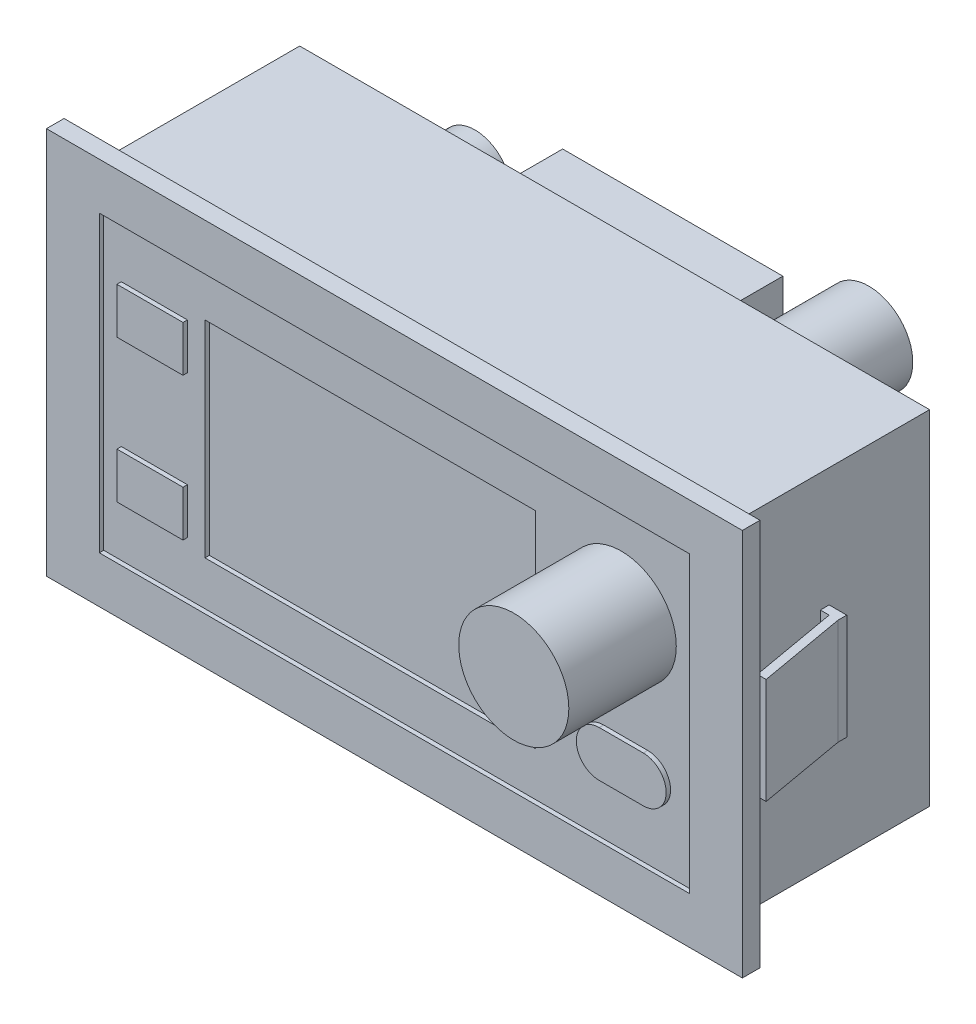
SolidWorks part; units mm, degrees
ref_plane "前视基准面" through (0, 0, 0) normal (0, 0, 1) x (1, 0, 0)
ref_plane "上视基准面" through (0, 0, 0) normal (0, 1, 0) x (1, 0, 0)
ref_plane "右视基准面" through (0, 0, 0) normal (1, 0, 0) x (0, 0, -1)
other "Configuration Table"
sketch "草图1" plane through (0, 0, 0) normal (0, 0, 1) x (1, 0, 0)
  line L0 (62.75, -30.1) -> (67.75, -30.1) construction
  line L1 (0, 0) -> (79, 0)
  line L2 (0, 0) -> (0, -44)
  line L3 (0, -44) -> (79, -44)
  line L4 (79, 0) -> (79, -44)
  line L5 (6, -5.3) -> (73, -5.3)
  line L6 (6, -5.3) -> (6, -38.7)
  line L7 (6, -38.7) -> (73, -38.7)
  line L8 (73, -5.3) -> (73, -38.7)
  line L11 (83.562, -21.4) -> (126.0812, -21.4) construction
  line L12 (17.5, -10.3) -> (55, -10.3)
  line L13 (17.5, -10.3) -> (17.5, -33.7)
  line L14 (17.5, -33.7) -> (55, -33.7)
  line L15 (55, -10.3) -> (55, -33.7)
  line L16 (8, -11.3) -> (15.5, -11.3)
  line L17 (8, -11.3) -> (8, -16.5)
  line L18 (8, -16.5) -> (15.5, -16.5)
  line L19 (15.5, -11.3) -> (15.5, -16.5)
  line L20 (8, -27.5) -> (15.5, -27.5)
  line L21 (8, -27.5) -> (8, -32.7)
  line L22 (8, -32.7) -> (15.5, -32.7)
  line L23 (15.5, -27.5) -> (15.5, -32.7)
  line L24 (59, 18.2066) -> (59, 8.2411) construction
  line L25 (62.75, -27.5) -> (67.75, -27.5)
  line L26 (62.75, -32.7) -> (67.75, -32.7)
  circle A0 centre (65.25, -15.15) radius 6.25
  arc A3 (62.75, -27.5) -> (62.75, -32.7) centre (62.75, -30.1) ccw
  arc A4 (67.75, -32.7) -> (67.75, -27.5) centre (67.75, -30.1) ccw
  point P11 (8, -13.9)
  point P14 (65.25, -30.1)
  point P35 (0, 0)
  point P36 (15.5, -30.1)
  dimension "D7" = 12.5
  dimension "D1" = 79
  dimension "D2" = 44
  dimension "D3" = 5.3
  dimension "D4" = 6
  dimension "D5" = 6
  dimension "D6" = 5.3
  dimension "D8" = 21.4
  dimension "D9" = 20
  dimension "D10" = 11.5
  dimension "D11" = 18
  dimension "D12" = 5
  dimension "D13" = 5
  dimension "D14" = 2
  dimension "D15" = 2
  dimension "D16" = 6
  dimension "D17" = 6
  dimension "D18" = 5.2
  dimension "D19" = 5.2
  dimension "D20" = 5
extrude "凸台-拉伸1" add sketch "草图1" against normal blind 12.2 contours A0
extrude "凸台-拉伸2" add sketch "草图1<3>" against normal blind 2 from surface separate body contours L4 L3 L2 L1 | L8 L7 L6 L5 starting at face at (71.5, -15.15, -12.2)
sketch "草图1<3>" plane through (0, 0, 0) normal (0, 0, 1) x (1, 0, 0) same geometry as "草图1"
extrude "凸台-拉伸3" add sketch "草图1<4>" along normal blind 1.5 from surface contours L8 L7 L6 L5 starting at face at (39.5, -22, -14.2)
sketch "草图1<4>" plane through (0, 0, 0) normal (0, 0, 1) x (1, 0, 0) same geometry as "草图1"
extrude "凸台-拉伸4" add sketch "草图1<5>" along normal blind 0.5 from surface separate body contours L26 A4 L25 A3 | L22 L23 L20 L21 | L18 L19 L16 L17 starting at face at (39.5, -22, -12.7)
sketch "草图1<5>" plane through (0, 0, 0) normal (0, 0, 1) x (1, 0, 0) same geometry as "草图1"
sketch "草图2" plane through (0, 0, -14.2) normal (0, 0, -1) x (-1, 0, 0)
  line L0 (-75.25, -2.5) -> (-75.25, 0) construction
  line L1 (-75.25, -2.5) -> (-3.75, -2.5)
  line L2 (-75.25, -2.5) -> (-75.25, -41.5)
  line L3 (-75.25, -41.5) -> (-3.75, -41.5)
  line L4 (-3.75, -2.5) -> (-3.75, -41.5)
  line L6 (-75.25, -2.5) -> (0, -2.5) construction
  line L7 (0, 0) -> (0, -44) construction
  line L8 (-3.75, -41.5) -> (-3.75, -44) construction
  line L9 (0, -44) -> (-79, -44) construction
  line L10 (-3.75, -41.5) -> (-79, -41.5) construction
  line L11 (-79, 0) -> (-79, -44) construction
  line L12 (0, 0) -> (-79, 0) construction
  point P4 (0, 0)
  dimension "D1" = 39
  dimension "D2" = 71.5
extrude "凸台-拉伸5" add sketch "草图2" along normal blind 23
extrude "切除-拉伸3" cut sketch "草图1<7>" against normal blind 0.5 from surface contours L14 L15 L12 L13 starting at face at (39.5, -22, -12.7)
sketch "草图1<7>" plane through (0, 0, 0) normal (0, 0, 1) x (1, 0, 0) same geometry as "草图1"
sketch "草图3" plane through (0, -41.5, 0) normal (0, -1, 0) x (1, 0, 0)
  line L0 (75.25, -25.8) -> (77.25, -25.8)
  line L1 (75.25, -37.2) -> (75.25, -14.2) construction
  line L2 (77.25, -25.8) -> (77.25, -24.8)
  line L3 (77.25, -24.8) -> (79, -14.9)
  line L4 (79, -14.9) -> (78, -14.9)
  line L5 (78, -14.9) -> (76.25, -24.8)
  line L6 (76.25, -24.8) -> (75.25, -24.8)
  line L7 (79, -14.2) -> (79, -12.2) construction
  line L8 (0, -14.2) -> (79, -14.2) construction
  line L9 (0, -12.2) -> (79, -12.2) construction
  line L10 (1.75, -25.8) -> (3.75, -25.8)
  line L11 (3.75, -37.2) -> (3.75, -14.2) construction
  line L12 (1.75, -24.8) -> (1.75, -25.8)
  line L13 (1.75, -24.8) -> (0, -14.9)
  line L14 (0, -14.9) -> (1, -14.9)
  line L15 (1, -14.9) -> (2.75, -24.8)
  line L16 (2.75, -24.8) -> (3.75, -24.8)
  line L17 (0, -14.2) -> (0, -12.2) construction
  point P18 (0, 0)
  point P22 (0, 0)
  line M6 (3.75, -14.2) -> (3.75, -37.2)
  line M8 (75.25, -37.2) -> (75.25, -14.2)
  dimension "D1" = 2
  dimension "D2" = 1
  dimension "D3" = 0.7
  dimension "D4" = 13.6
extrude "凸台-拉伸6" add sketch "草图3" against normal offset from surface (12 mm away) 13.5 from offset 13.5 contours L16 L15 L14 L13 L12 L10 M6 | L5 L6 L0 L2 L3 L4 M8 region at (77.3939, -41.5, -20.766) region at (1.6061, -41.5, -20.766) up to face at (39.5, -2.5, -25.7) offset against normal yes
sketch "草图4" plane through (0, -41.5, 0) normal (0, -1, 0) x (1, 0, 0)
  line L0 (29, -22.2) -> (50, -22.2)
  line L1 (27.5, -23.7) -> (27.5, -37.2)
  line L2 (75.25, -37.2) -> (3.75, -37.2) construction
  line L3 (51.5, -23.7) -> (51.5, -37.2)
  line L6 (29, -29) -> (27.5, -29) construction
  line L7 (29, -41) -> (50, -41)
  line L8 (29, -41) -> (29, -29)
  line L9 (29, -29) -> (50, -29)
  line L10 (50, -41) -> (50, -29)
  line L11 (50, -29) -> (51.5, -29) construction
  line L12 (27.5, -33.9386) -> (3.75, -33.9386) construction
  line L13 (3.75, -37.2) -> (3.75, -14.2) construction
  line L14 (51.5, -33.9386) -> (75.25, -33.9386) construction
  line L15 (75.25, -37.2) -> (75.25, -14.2) construction
  circle A0 centre (29, -23.7) radius 1.5
  circle A1 centre (50, -23.7) radius 1.5
  line M8 (3.75, -37.2) -> (75.25, -37.2)
  dimension "D4" = 3
  dimension "D1" = 1.5
  dimension "D2" = 12
  dimension "D3" = 15
  dimension "D5" = 21
  dimension "D6" = 3.8
extrude "切除-拉伸4" cut sketch "草图4" against normal blind 10 contours A1 L0 A0 L1 L3 M8 | A1 | A0 | L7 L10 L9 L8 region at (39.5, -41.5, -26.841) region at (29, -41.5, -23.7) region at (50, -41.5, -23.7) region at (39.5, -41.5, -33.1)
extrude "凸台-拉伸7" add sketch "草图4<3>" against normal blind 8 separate body contours L7 L10 L9 L8
sketch "草图4<3>" plane through (0, -41.5, 0) normal (0, -1, 0) x (1, 0, 0) same geometry as "草图4"
sketch "草图7" plane through (0, 0, -41) normal (0, 0, -1) x (-1, 0, 0)
  line L1 (-51.5, -41.5) -> (-27.5, -41.5)
  line L2 (-51.5, -41.5) -> (-51.5, -21.5)
  line L3 (-51.5, -21.5) -> (-27.5, -21.5)
  line L4 (-27.5, -41.5) -> (-27.5, -21.5)
  point P5 (0, 0)
  point P6 (0, 0)
  dimension "D1" = 20
extrude "凸台-拉伸8" add sketch "草图7" along normal blind 2 from surface starting at face at (39.5, -37.5, -29)
sketch "草图8" plane through (0, 0, -37.2) normal (0, 0, -1) x (-1, 0, 0)
  line L0 (-3.75, -2.5) -> (-75.25, -2.5) construction
  line L1 (-74.05, -3.7) -> (-4.95, -3.7)
  line L2 (-74.05, -3.7) -> (-74.05, -40.3)
  line L3 (-74.05, -40.3) -> (-4.95, -40.3)
  line L4 (-4.95, -3.7) -> (-4.95, -40.3)
  line L5 (-51.5, -40.3) -> (-27.5, -40.3)
  line L6 (-51.5, -40.3) -> (-51.5, -31.5)
  line L7 (-51.5, -31.5) -> (-27.5, -31.5)
  line L8 (-27.5, -40.3) -> (-27.5, -31.5)
  line L9 (-75.25, -2.5) -> (-75.25, -41.5) construction
  line L10 (-75.25, -41.5) -> (-51.5, -41.5) construction
  line L11 (-3.75, -16) -> (-3.75, -28) construction
  line L12 (-51.5, -31.5) -> (-51.5, -41.5) construction
  line L13 (-27.5, -31.5) -> (-51.5, -31.5) construction
  line L14 (-27.5, -31.5) -> (-27.5, -41.5) construction
  line M10 (-51.5, -41.5) -> (-51.5, -31.5)
  line M11 (-51.5, -31.5) -> (-27.5, -31.5)
  line M12 (-27.5, -31.5) -> (-27.5, -41.5)
  dimension "D1" = 1.2
  dimension "D2" = 1.2
  dimension "D3" = 1.2
  dimension "D4" = 1.2
extrude "切除-拉伸5" cut sketch "草图8" against normal up to surface (6.2 mm away) contours L4 L1 L2 L3 M10 M11 M12 region at (39.5, -20.7335, -37.2) up to face at (39.5, -37, -31)
sketch "草图9" plane through (0, 0, -31) normal (0, 0, -1) x (-1, 0, 0)
  line L0 (-16.65, -16) -> (-4.95, -16)
  line L1 (-52, -4.3) -> (-27, -4.3)
  line L2 (-52, -4.3) -> (-52, -29.3)
  line L3 (-52, -29.3) -> (-27, -29.3)
  line L4 (-27, -4.3) -> (-27, -29.3)
  line L5 (-25.25, -18.2) -> (-5.25, -18.2)
  line L6 (-25.25, -18.2) -> (-25.25, -27)
  line L7 (-25.25, -27) -> (-5.25, -27)
  line L8 (-5.25, -18.2) -> (-5.25, -27)
  line L9 (-4.95, -40.3) -> (-4.95, -3.7) construction
  line L10 (-20.75, -11.9) -> (-20.75, -3.7)
  line L11 (-4.95, -3.7) -> (-74.05, -3.7) construction
  line L12 (-52, -4.3) -> (-74.05, -4.3) construction
  line L13 (-74.05, -3.7) -> (-74.05, -40.3) construction
  line L14 (-27, -4.3) -> (-4.95, -4.3) construction
  line L15 (-4.95, -3.7) -> (-4.95, -40.3) construction
  line L16 (-52.65, -9.5) -> (-52.65, -3.7)
  line L17 (-74.05, -3.7) -> (-4.95, -3.7) construction
  line L18 (-3.75, -41.5) -> (-3.75, -2.5) construction
  line L19 (-3.75, -2.5) -> (-75.25, -2.5) construction
  line L20 (-57.65, -14.5) -> (-74.05, -14.5)
  line L21 (-3.75, -2.5) -> (-75.25, -2.5) construction
  line L22 (-56.75, -35.2) -> (-56.75, -41.5)
  line L23 (-75.25, -41.5) -> (-3.75, -41.5) construction
  line L24 (-60.85, -31.1) -> (-75.25, -31.1)
  line L25 (-75.25, -2.5) -> (-75.25, -41.5) construction
  line L26 (-75.25, -41.5) -> (-51.5, -41.5) construction
  line L27 (-20.75, -33.5) -> (-20.75, -44)
  line L28 (0, -44) -> (-79, -44) construction
  line L29 (-15.75, -28.5) -> (-3.75, -28.5)
  line L30 (-3.75, -16) -> (-3.75, -28) construction
  line L31 (-27.5, -41.5) -> (-3.75, -41.5) construction
  circle A0 centre (-57.65, -9.5) radius 5
  circle A1 centre (-60.85, -35.2) radius 4.1
  circle A2 centre (-15.75, -33.5) radius 5
  circle A3 centre (-16.65, -11.9) radius 4.1
  dimension "D1" = 8.2
  dimension "D2" = 10
  dimension "D3" = 25
  dimension "D4" = 17
  dimension "D5" = 13.5
  dimension "D6" = 1.8
  dimension "D7" = 21.4
  dimension "D8" = 12
  dimension "D9" = 18.5
  dimension "D10" = 10.4
  dimension "D11" = 13
  dimension "D12" = 17
  dimension "D13" = 20
  dimension "D14" = 8.8
  dimension "D15" = 21.5
  dimension "D16" = 24.5
extrude "凸台-拉伸9" add sketch "草图9" along normal offset from surface (12.8 mm away) 6.6 contours A0 L2 L3 L4 L1 region at (39.5, -16.8, -31) up to face at (39.5, -28.3, -37.2) offset beyond the face yes
extrude "凸台-拉伸10" add sketch "草图9<3>" along normal offset from surface (13.2 mm away) 7 contours A3 region at (16.65, -11.9, -31) up to face at (39.5, -28.3, -37.2) offset beyond the face yes
sketch "草图9<3>" plane through (0, 0, -31) normal (0, 0, -1) x (-1, 0, 0) same geometry as "草图9"
extrude "凸台-拉伸12" add sketch "草图9<5>" along normal offset from surface (16.9 mm away) 10.7 contours A0 | A2 region at (57.65, -9.5, -31) region at (15.75, -33.5, -31) up to face at (39.5, -28.3, -37.2) offset beyond the face yes
sketch "草图9<5>" plane through (0, 0, -31) normal (0, 0, -1) x (-1, 0, 0) same geometry as "草图9"
extrude "凸台-拉伸13" add sketch "草图9<6>" along normal offset from surface (16.5 mm away) 10.3 contours A1 region at (60.85, -35.2, -31) up to face at (39.5, -28.3, -37.2) offset beyond the face yes
sketch "草图9<6>" plane through (0, 0, -31) normal (0, 0, -1) x (-1, 0, 0) same geometry as "草图9"
extrude "凸台-拉伸14" add sketch "草图9<7>" along normal offset from surface (18.3 mm away) 12.1 contours L8 L5 L6 L7 region at (15.25, -22.6, -31) up to face at (39.5, -28.3, -37.2) offset beyond the face yes
sketch "草图9<7>" plane through (0, 0, -31) normal (0, 0, -1) x (-1, 0, 0) same geometry as "草图9"
